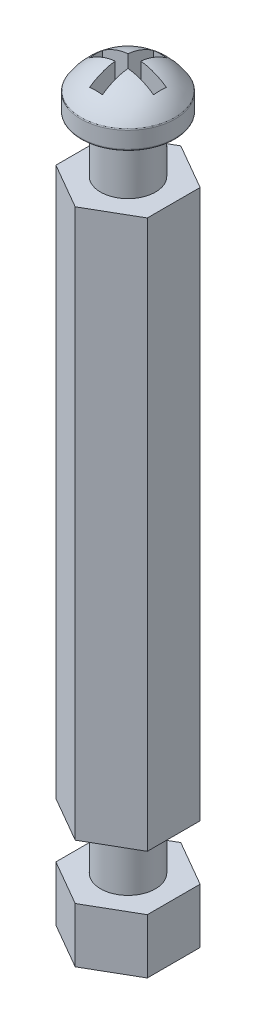
SolidWorks part; units mm, degrees
ref_plane "Front Plane" through (0, 0, 0) normal (0, 0, 1) x (1, 0, 0)
ref_plane "Top Plane" through (0, 0, 0) normal (0, 1, 0) x (1, 0, 0)
ref_plane "Right Plane" through (0, 0, 0) normal (1, 0, 0) x (0, 0, -1)
sketch "Sketch1" plane through (0, 0, 0) normal (0, 1, 0) x (1, 0, 0)
  line L1 (2.5, 1.4434) -> (0, 2.8868)
  line L2 (0, 2.8868) -> (-2.5, 1.4434)
  line L3 (-2.5, 1.4434) -> (-2.5, -1.4434)
  line L4 (-2.5, -1.4434) -> (0, -2.8868)
  line L5 (0, -2.8868) -> (2.5, -1.4434)
  line L6 (2.5, -1.4434) -> (2.5, 1.4434)
  circle A0 centre (0, 0) radius 2.5 construction
  circle A1 centre (0, 0) radius 1.5
  dimension "D1" = 3
  dimension "D2" = 5
extrude "Boss-Extrude1" add sketch "Sketch1" along normal blind 30 contours A1 | L5 L6 L1 L2 L3 L4 A1 region at (2.4236, 0, 0) region at (0, 0, 0)
extrude "Boss-Extrude2" add sketch "Sketch1<4>" against normal blind 6 contours A1 region at (0, 0, 0)
sketch "Sketch1<4>" plane through (0, 0, 0) normal (0, 1, 0) x (1, 0, 0) same geometry as "Sketch1"
sketch "Sketch3" plane through (0, 0, 0) normal (0, 0, 1) x (1, 0, 0)
  line L0 (1.5, -6) -> (1.5, 0) construction
  line L1 (0, 30) -> (1.5, 30)
  line L2 (0, 30) -> (0, 33)
  line L3 (0, 33) -> (1.5, 33)
  line L4 (1.5, 30) -> (1.5, 33)
  line L5 (0, 30) -> (0, 0) construction
  line L6 (1.5, 33) -> (3.6588, 33)
  line L7 (0, 33) -> (0, 35.5)
  line L8 (0, 30) -> (0, -6) construction
  line L9 (-1.5, -6) -> (1.5, -6) construction
  line L10 (0, 12) -> (3.9182, 12) construction
  line L11 (0, -9) -> (0, -11.5)
  line L12 (1.5, -9) -> (3.6588, -9)
  line L13 (1.5, -6) -> (1.5, -9)
  line L14 (0, -9) -> (1.5, -9)
  line L15 (0, -6) -> (0, -9)
  line L16 (0, -6) -> (1.5, -6)
  line L17 (2.5777, 34) -> (2.5777, 33)
  circle A0 centre (0, 32.5) radius 3
  circle A1 centre (2.4527, 34) radius 0.125
  circle A2 centre (0, -8.5) radius 3
  circle A3 centre (2.4527, -10) radius 0.125
  dimension "D2" = 0.25
  dimension "D5" = 6
  dimension "D1" = 3
  dimension "D3" = 1
  dimension "D4" = 0.5
revolve "Revolve1" add sketch "Sketch3" angle 360 about L8 region at (0.75, 31.5, 0) region at (1.1363, 34.0777, 0) region at (2.4527, 34, 0)
ref_plane "Plane1" through (0, 40, 0) normal (0, 1, 0) x (1, 0, 0)
sketch "Sketch4" plane through (0, 40, 0) normal (0, 1, 0) x (1, 0, 0)
  line L1 (-1.75, -0.35) -> (1.75, -0.35)
  line L2 (-1.75, -0.35) -> (-1.75, 0.35)
  line L3 (-1.75, 0.35) -> (1.75, 0.35)
  line L4 (1.75, -0.35) -> (1.75, 0.35)
  line L5 (-1.75, -0.35) -> (1.75, 0.35) construction
  line L6 (-1.75, 0.35) -> (1.75, -0.35) construction
  line L7 (-0.35, -1.75) -> (0.35, -1.75)
  line L8 (-0.35, -1.75) -> (-0.35, 1.75)
  line L9 (-0.35, 1.75) -> (0.35, 1.75)
  line L10 (0.35, -1.75) -> (0.35, 1.75)
  line L11 (-0.35, -1.75) -> (0.35, 1.75) construction
  line L12 (-0.35, 1.75) -> (0.35, -1.75) construction
  point P0 (0, 0)
  point P6 (0, 0)
  dimension "D1" = 0.7
  dimension "D2" = 3.5
extrude "Cut-Extrude1" cut sketch "Sketch4" against normal blind 7 contours L7 L10 L1 L8 | L10 L1 L4 L3 | L3 L10 L9 L8 | L1 L8 L3 L2 | L1 L10 L3 L8 region at (-1.05, 40, 0) region at (0, 40, 0) region at (0, 40, 1.05) region at (1.05, 40, 0) region at (0, 40, -1.05)
fillet "Fillet1" radius 0.1 1 edges at (-2.5777, 33, 0)
sketch "Sketch5" plane through (0, -6, 0) normal (0, -1, 0) x (1, 0, 0)
  line L6 (2.5, 1.4434) -> (0, 2.8868)
  line L7 (0, 2.8868) -> (-2.5, 1.4434)
  line L8 (-2.5, 1.4434) -> (-2.5, -1.4434)
  line L9 (-2.5, -1.4434) -> (0, -2.8868)
  line L10 (0, -2.8868) -> (2.5, -1.4434)
  line L11 (2.5, -1.4434) -> (2.5, 1.4434)
  line L12 (2.5, 1.4434) -> (0, 2.8868)
  line L13 (0, 2.8868) -> (-2.5, 1.4434)
  line L14 (-2.5, 1.4434) -> (-2.5, -1.4434)
  line L15 (-2.5, -1.4434) -> (0, -2.8868)
  line L16 (0, -2.8868) -> (2.5, -1.4434)
  line L17 (2.5, -1.4434) -> (2.5, 1.4434)
  circle A0 centre (0, 0) radius 1.5 construction
  circle A1 centre (0, 0) radius 1.5
  dimension "D1" = 0
extrude "Boss-Extrude3" add sketch "Sketch5" against normal blind 3 separate body
